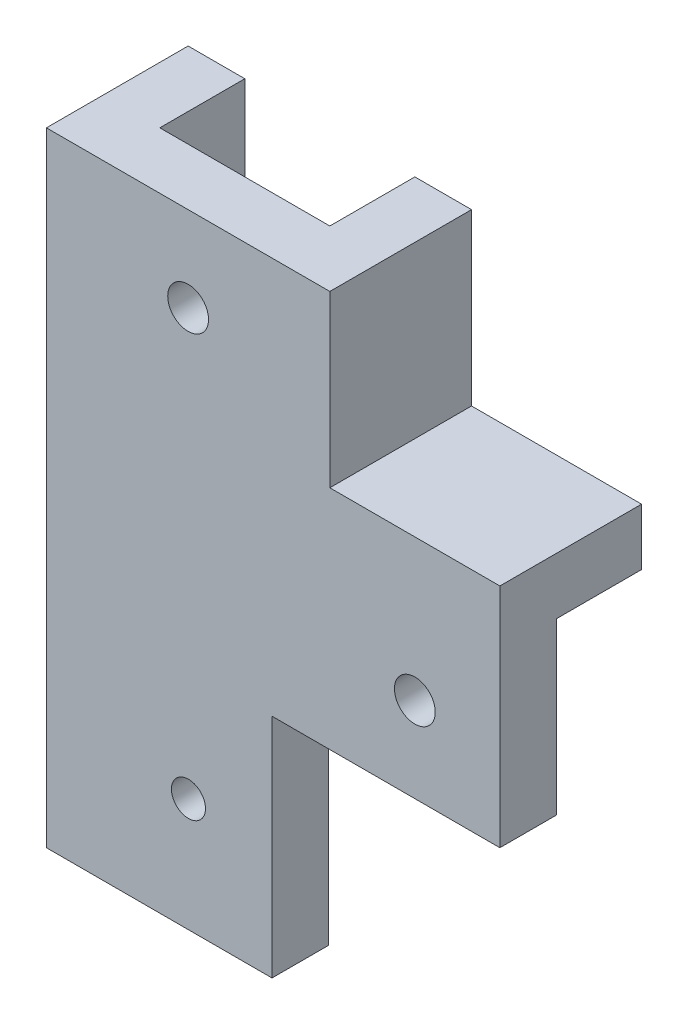
SolidWorks part; units mm, degrees
ref_plane "前视基准面" through (0, 0, 0) normal (0, 0, 1) x (1, 0, 0)
ref_plane "上视基准面" through (0, 0, 0) normal (0, 1, 0) x (1, 0, 0)
ref_plane "右视基准面" through (0, 0, 0) normal (1, 0, 0) x (0, 0, -1)
sketch "Sketch1" plane through (0, 0, 0) normal (0, 0, 1) x (1, 0, 0)
  line L0 (7.3701, -25.8068) -> (27.4701, -25.8068)
  line L3 (-7.5299, 9.1932) -> (7.4701, 9.1932)
  line L4 (-7.5299, 9.1932) -> (-7.5299, -25.8068)
  line L6 (7.4701, 9.1932) -> (7.4701, -10.8068)
  line L7 (27.4701, -25.8068) -> (27.4701, -10.8068)
  line L8 (27.4701, -10.8068) -> (7.4701, -10.8068)
  line L12 (-7.5299, -25.8068) -> (7.3701, -25.8068)
  dimension "D1" = 15
  dimension "D2" = 35
  dimension "D3" = 35
  dimension "D4" = 15
extrude "Boss-Extrude1" add sketch "Sketch1" along normal blind 5
sketch "Sketch2" plane through (0, 0, 0) normal (0, 0, -1) x (-1, 0, 0)
  line L0 (-7.4701, 9.1932) -> (-12.4701, 9.1932)
  line L1 (-12.4701, 9.1932) -> (-12.4701, -5.8068)
  line L2 (-12.4701, -5.8068) -> (-27.4701, -5.8068)
  line L3 (-27.4701, -10.8068) -> (-27.4701, -5.8068)
  line L4 (-27.4701, -10.8068) -> (-7.4701, -10.8068)
  line L5 (-7.4701, -10.8068) -> (-7.4701, 9.1932)
  dimension "D1" = 5
  dimension "D2" = 5
extrude "Boss-Extrude2" add sketch "Sketch2" along normal blind 7.5 separate body
sketch "Sketch3" plane through (0, 0, 0) normal (0, 0, -1) x (-1, 0, 0)
  line L0 (7.5299, 9.1932) -> (12.5299, 9.1932)
  line L2 (12.5299, -45.8068) -> (12.5299, 9.1932)
  line L3 (7.5299, -25.8068) -> (7.5299, 9.1932)
  line L5 (7.5299, -25.8068) -> (7.5299, -45.8068)
  line L6 (7.5299, -45.8068) -> (12.5299, -45.8068)
  dimension "D1" = 5
  dimension "D2" = 55
extrude "Boss-Extrude3" add sketch "Sketch3" along normal blind 7.5 separate body
sketch "Sketch4" plane through (0, 0, 0) normal (0, 0, -1) x (-1, 0, 0)
  line L0 (-27.4701, -10.8068) -> (-7.4701, -10.8068) construction
  line L1 (-27.4701, -25.8068) -> (-27.4701, -10.8068) construction
  line L2 (-7.4701, -10.8068) -> (-7.4701, 9.1932) construction
  line L3 (-7.4701, 9.1932) -> (7.5299, 9.1932) construction
  circle A0 centre (0.0299, 1.6932) radius 1.8
  circle A1 centre (-19.9701, -18.3068) radius 1.8
  dimension "D1" = 3.6
  dimension "D2" = 3.6
  dimension "D3" = 7.5
  dimension "D4" = 7.5
  dimension "D5" = 7.5
  dimension "D6" = 7.5
extrude "Cut-Extrude1" cut sketch "Sketch4" against normal through all
sketch "Sketch6" plane through (0, 0, 5) normal (0, 0, 1) x (1, 0, 0)
  line L0 (-7.5299, -25.8068) -> (-7.5299, -45.8068)
  line L1 (-7.5299, -25.8068) -> (27.4701, -25.8068) construction
  line L2 (-7.5299, -45.8068) -> (7.3701, -45.8068)
  line L3 (7.3701, -45.8068) -> (7.3701, -25.8068)
  line L4 (7.3701, -25.8068) -> (-7.5299, -25.8068)
  dimension "D1" = 14.9
  dimension "D2" = 20
extrude "Boss-Extrude4" add sketch "Sketch6" against normal blind 5
sketch "Sketch8" plane through (0, 0, 5) normal (0, 0, 1) x (1, 0, 0)
  line L0 (-7.5299, -45.8068) -> (7.3701, -45.8068) construction
  circle A0 centre (0, -35.8068) radius 1.5
  dimension "D1" = 3
  dimension "D2" = 10
extrude "Cut-Extrude3" cut sketch "Sketch8" against normal through all contours A0
sketch "Sketch9" plane through (0, 0, 5) normal (0, 0, 1) x (1, 0, 0)
  line L1 (-12.5299, 9.1932) -> (-7.5299, 9.1932)
  line L2 (-12.5299, 9.1932) -> (-12.5299, -45.8068)
  line L3 (-12.5299, -45.8068) -> (-7.5299, -45.8068)
  line L4 (-7.5299, 9.1932) -> (-7.5299, -45.8068)
extrude "Boss-Extrude5" add sketch "Sketch9" against normal blind 5
sketch "Sketch10" plane through (0, 0, 0) normal (0, 0, 1) x (1, 0, 0)
  line L0 (7.4701, 9.1932) -> (12.4701, 9.1932)
  line L1 (7.4701, 9.1932) -> (12.4701, 9.1932) construction
  line L2 (12.4701, 9.1932) -> (12.4701, -5.8068)
  line L3 (12.4701, -5.8068) -> (27.4701, -5.8068)
  line L4 (12.4701, -5.8068) -> (27.4701, -5.8068) construction
  line L5 (27.4701, -5.8068) -> (27.4701, -10.8068) construction
  line L6 (27.4701, -5.8068) -> (27.4701, -10.8068)
  line L7 (27.4701, -10.8068) -> (7.4701, -10.8068)
  line L8 (7.4701, -10.8068) -> (7.4701, 9.1932)
extrude "Boss-Extrude6" add sketch "Sketch10" along normal blind 5
